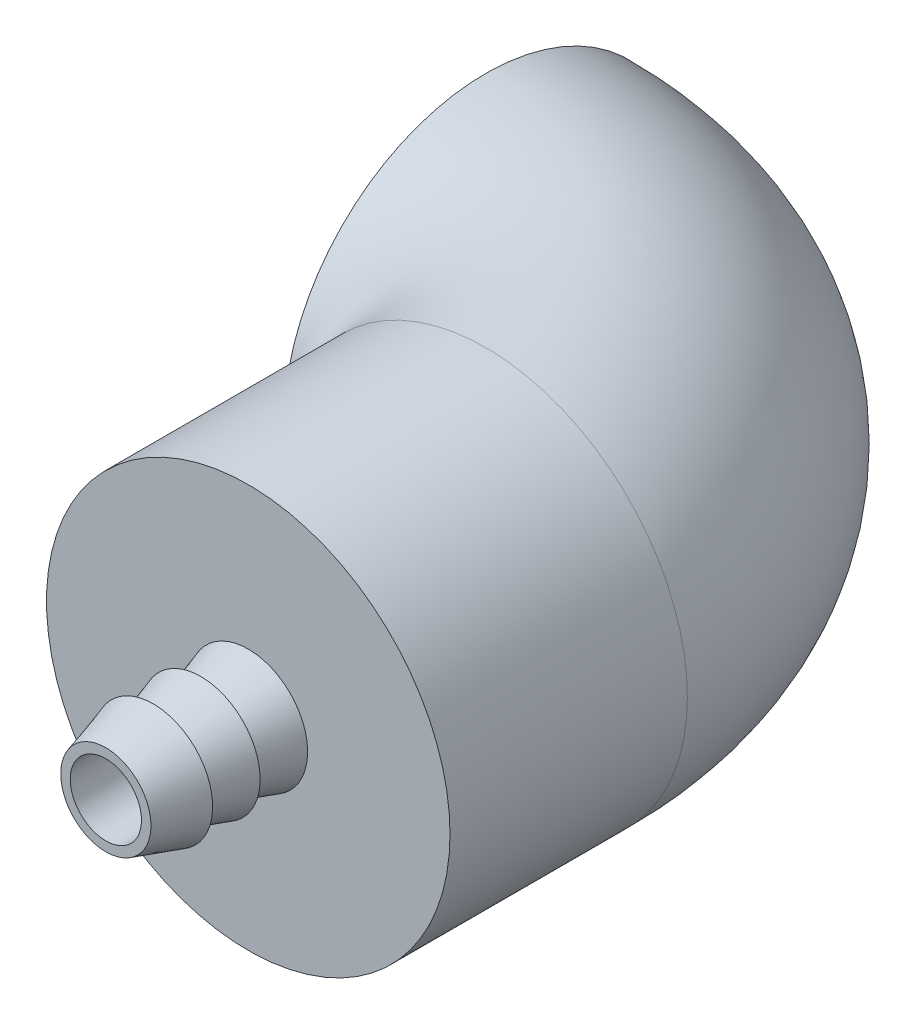
SolidWorks part; units mm, degrees
ref_plane "前视基准面" through (0, 0, 0) normal (0, 0, 1) x (1, 0, 0)
ref_plane "上视基准面" through (0, 0, 0) normal (0, 1, 0) x (1, 0, 0)
ref_plane "右视基准面" through (0, 0, 0) normal (1, 0, 0) x (0, 0, -1)
other "Configuration Table"
sketch "草图2" plane through (0, 0, 0) normal (0, 0, 1) x (1, 0, 0)
  circle A0 centre (0, 0) radius 8.5
  circle A1 centre (0, 0) radius 8
  dimension "D1" = 17
  dimension "D2" = 16
sketch "草图3" plane through (0, 0, 0) normal (0, 1, 0) x (1, 0, 0)
  line L0 (0, 0) -> (0, 10)
  line L1 (-8, 0) -> (8, 0) construction
  arc A0 (0, 10) -> (-10, 20) centre (-10, 10) ccw
  dimension "D1" = 10
sweep "扫描5" add profiles "草图2" path "草图3"
sketch "草图4" plane through (0, 0, 0) normal (0, 0, 1) x (1, 0, 0)
  circle A0 centre (0, 0) radius 8.5
  circle A1 centre (0, 0) radius 1.5
  dimension "D1" = 3
extrude "凸台-拉伸1" add sketch "草图4" against normal blind 1
sketch "草图5" plane through (0, 0, 0) normal (0, 1, 0) x (1, 0, 0)
  line L0 (0, 0) -> (1.5, 0) construction
  line L1 (-8.5, 0) -> (8.5, 0) construction
  line L2 (1.5, 0) -> (1.5, -6)
  line L3 (1.5, -6) -> (1.9, -6)
  line L4 (1.9, -6) -> (2.5, -4)
  line L5 (2.5, -4) -> (1.9, -4)
  line L6 (1.9, -4) -> (2.5, -2)
  line L7 (2.5, -2) -> (1.9, -2)
  line L8 (1.9, -2) -> (2.5, 0)
  line L9 (2.5, 0) -> (1.5, 0)
  line L10 (0, 0) -> (0, -6) construction
  dimension "D1" = 1.5
  dimension "D2" = 6
  dimension "D3" = 2
  dimension "D4" = 2
  dimension "D5" = 1
  dimension "D6" = 1
  dimension "D7" = 1
  dimension "D8" = 0.4
  dimension "D9" = 0.4
  dimension "D10" = 0.4
revolve "旋转1" add sketch "草图5" angle 360 about L10
